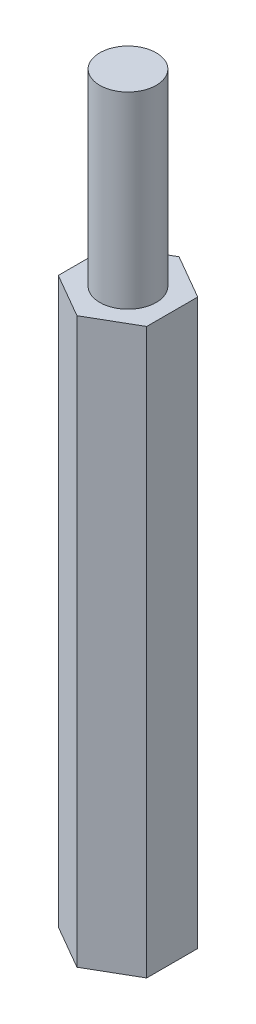
SolidWorks part; units mm, degrees
ref_plane "Front Plane" through (0, 0, 0) normal (0, 0, 1) x (1, 0, 0)
ref_plane "Top Plane" through (0, 0, 0) normal (0, 1, 0) x (1, 0, 0)
ref_plane "Right Plane" through (0, 0, 0) normal (1, 0, 0) x (0, 0, -1)
sketch "Sketch1" plane through (0, 0, 0) normal (0, 1, 0) x (1, 0, 0)
  line L1 (0, 2.7135) -> (-2.35, 1.3568)
  line L2 (-2.35, 1.3568) -> (-2.35, -1.3568)
  line L3 (-2.35, -1.3568) -> (0, -2.7135)
  line L4 (0, -2.7135) -> (2.35, -1.3568)
  line L5 (2.35, -1.3568) -> (2.35, 1.3568)
  line L6 (2.35, 1.3568) -> (0, 2.7135)
  circle A0 centre (0, 0) radius 2.35 construction
  dimension "D1" = 4.7
extrude "Boss-Extrude1" add sketch "Sketch1" along normal blind 30
sketch "Sketch2" plane through (0, 30, 0) normal (0, 1, 0) x (1, 0, 0)
  circle A0 centre (0, 0) radius 1.5
  dimension "D1" = 3
extrude "Boss-Extrude2" add sketch "Sketch2" along normal blind 10
sketch "Sketch5" plane through (0, 0, 0) normal (0, -1, 0) x (1, 0, 0)
  circle A0 centre (0, 0) radius 1.5
  dimension "D1" = 3
extrude "Cut-Extrude1" cut sketch "Sketch5" against normal blind 10
